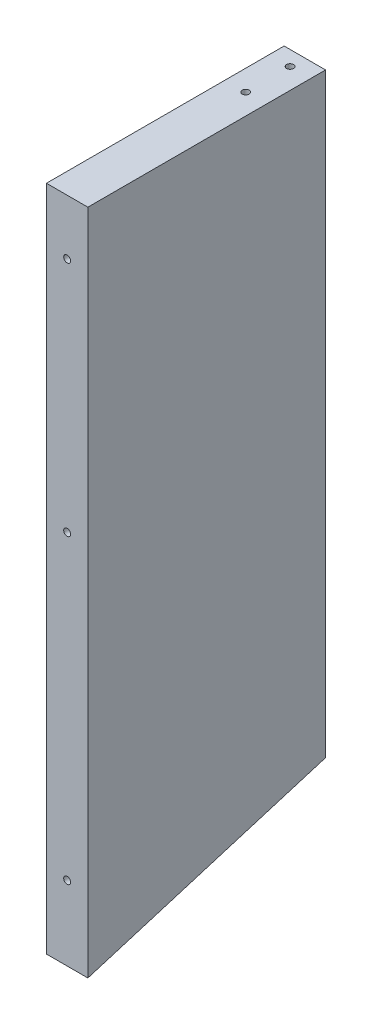
SolidWorks part; units mm, degrees
material "Beech"
ref_plane "Front Plane" through (0, 0, 0) normal (0, 0, 1) x (1, 0, 0)
ref_plane "Top Plane" through (0, 0, 0) normal (0, 1, 0) x (1, 0, 0)
ref_plane "Right Plane" through (0, 0, 0) normal (1, 0, 0) x (0, 0, -1)
sketch "Sketch1" plane through (0, 0, 0) normal (0, 0, 1) x (1, 0, 0)
  line L0 (-124.0045, -157.3) -> (-124.0045, -427.3421) construction
  line L1 (-124.0045, -157.3) -> (-124.0045, -144.6) construction
  line L2 (-244.0045, -144.6) -> (-4.0045, -144.6) construction
  line L7 (93.2955, -427.3421) -> (-341.3045, -427.3421) construction
  line L9 (8.6955, -157.3) -> (-256.7045, -157.3) construction
  line L10 (-133.5295, -157.3) -> (-133.5295, -427.3421)
  line L11 (-114.4795, -157.3) -> (-114.4795, -427.3421)
  line L12 (-133.5295, -157.3) -> (-114.4795, -157.3)
  line L13 (-133.5295, -427.3421) -> (-114.4795, -427.3421)
  dimension "D1" = 9.525
  dimension "D2" = 9.525
extrude "Boss-Extrude1" add sketch "Sketch1" along normal up to surface (33.95 mm away)
sketch "Sketch2" plane through (0, 0, 33.95) normal (0, 0, 1) x (1, 0, 0)
  line L0 (-256.7045, -157.3) -> (8.6955, -157.3) construction
  line L4 (-114.4795, -427.3421) -> (-114.4795, -157.3)
  line L5 (-114.4795, -157.3) -> (-133.5295, -157.3)
  line L6 (-133.5295, -157.3) -> (-133.5295, -427.3421)
  line L7 (-133.5295, -427.3421) -> (-114.4795, -427.3421)
  line L8 (-114.4795, -427.3421) -> (-114.4795, -157.3)
  line L9 (-114.4795, -157.3) -> (-133.5295, -157.3)
  line L10 (-133.5295, -157.3) -> (-133.5295, -427.3421)
  line L11 (-133.5295, -427.3421) -> (-114.4795, -427.3421)
  dimension "D1" = 0
extrude "Boss-Extrude2" add sketch "Sketch2" along normal up to surface (75.35 mm away)
sketch "Sketch3" plane through (-133.5295, 0, 0) normal (-1, 0, 0) x (0, 0, 1)
  line L0 (109.3, -427.3421) -> (109.3, -464.2661)
  line L1 (109.3, -464.2661) -> (0, -431.1858)
  line L2 (0, -431.1858) -> (0, -427.3421)
  line L3 (0, -427.3421) -> (109.3, -427.3421)
  line L4 (109.3, -427.3421) -> (0, -427.3421) construction
  line L5 (-12.7, -427.3421) -> (522.1409, -589.2145) construction
extrude "Boss-Extrude3" add sketch "Sketch3" against normal through all
hole_wizard "Hole1" positions "Sketch4" profile "Sketch5" legacy
sketch "Sketch4" plane through (-124.0045, 10.4243, 122) normal (0, 0, 1) x (-1, 0, 0)
  line L1 (0, 465.9538) -> (0, 167.7243) construction
  point P1 (113.65, 128.8076)
  point P3 (113.65, 23.941)
  point P5 (-94.6, 161.3743)
  point P7 (94.6, 161.3743)
  point P9 (0, 161.3743)
  point P11 (0, 193.1243)
  point P13 (0, 440.5538)
  point P15 (0, 301.9704)
  point P17 (40.9792, 301.9704)
  point P19 (166.7958, 301.9704)
  point P21 (207.775, 440.5538)
  point P23 (207.775, 333.0214)
  point P25 (207.775, 225.489)
  point P27 (207.775, 137.4243)
  point P29 (207.775, 10.4243)
  point P33 (-207.775, 10.4243)
  point P34 (-207.775, 137.4243)
  point P35 (-207.775, 225.489)
  point P36 (-207.775, 333.0214)
  point P37 (-207.775, 440.5538)
  point P38 (-166.7958, 301.9704)
  point P39 (-40.9792, 301.9704)
  point P40 (-113.65, 23.941)
  point P41 (-113.65, 128.8076)
sketch "Sketch5" plane through (-237.6545, -118.3833, 122) normal (1, 0, 0) x (0, -1, 0)
  line L0 (0, 0) -> (0, 32.7039)
  line L1 (0, 32.7039) -> (1.5875, 31.75)
  line L2 (1.5875, 31.75) -> (1.5875, 4.0177)
  line L3 (1.5875, 4.0177) -> (5.08, 0)
  line L4 (5.08, 0) -> (0, 0)
  line L5 (0, -14.3089) -> (0, 102.4216) construction
  line L6 (0, 32.7039) -> (-1.5875, 31.75) construction
  line L7 (-1.5875, 4.0177) -> (-5.08, 0) construction
  dimension "Diameter" = 3.175
  dimension "Depth" = 31.75
  dimension "C-Sink Diameter" = 10.16
  dimension "C-Sink Angle" = 82
  dimension "Drill Angle" = 118
hole_wizard "Hole3" positions "Sketch7" profile "Sketch8" legacy
sketch "Sketch7" plane through (-124.0045, -144.6, -155.2867) normal (0, 1, 0) x (-1, 0, 0)
  line L0 (0, 155.2867) -> (0, 189.2867) construction
  line L9 (0, 189.2867) -> (0, 182.4867)
  line L10 (0, 182.4867) -> (0, 175.6867)
  line L11 (0, 175.6867) -> (0, 168.8867)
  line L12 (0, 168.8867) -> (0, 162.0867)
  line L13 (0, 162.0867) -> (0, 155.2867)
  point P26 (0, 182.4867)
  point P32 (0, 162.0867)
sketch "Sketch8" plane through (-124.0045, -144.6, 6.8) normal (1, 0, 0) x (0, 0, 1)
  line L0 (0, 0) -> (0, 32.7039)
  line L1 (0, 32.7039) -> (1.5875, 31.75)
  line L2 (1.5875, 31.75) -> (1.5875, 4.0177)
  line L3 (1.5875, 4.0177) -> (5.08, 0)
  line L4 (5.08, 0) -> (0, 0)
  line L5 (0, -14.3089) -> (0, 102.4216) construction
  line L6 (0, 32.7039) -> (-1.5875, 31.75) construction
  line L7 (-1.5875, 4.0177) -> (-5.08, 0) construction
  dimension "Diameter" = 3.175
  dimension "Depth" = 31.75
  dimension "C-Sink Diameter" = 10.16
  dimension "C-Sink Angle" = 82
  dimension "Drill Angle" = 118
hole_wizard "Hole4" positions "Sketch9" profile "Sketch10" legacy
sketch "Sketch9" plane through (-124.0045, 10.4243, -12.7) normal (0, 0, -1) x (1, 0, 0)
  line L12 (0, 0) -> (0, 155.0243) construction
  point P0 (-207.775, 333.0214)
  point P3 (-207.775, 225.489)
  point P6 (-207.775, 137.4243)
  point P9 (-172.1667, 4.0743)
  point P12 (-146.0833, 4.0743)
  point P15 (-94.6, 161.3743)
  point P18 (0, 161.3743)
  point P21 (94.6, 161.3743)
  point P24 (146.0833, 4.0743)
  point P27 (172.1667, 4.0743)
  point P30 (207.775, 137.4243)
  point P33 (207.775, 225.489)
  point P36 (207.775, 333.0214)
  point P39 (166.7958, 301.9704)
  point P42 (40.9792, 301.9704)
  point P45 (-40.9792, 301.9704)
  point P48 (-166.7958, 301.9704)
  point P51 (0, 193.1243)
  point P54 (0, 301.9704)
  point P57 (0, 412.3664)
  point P80 (-126.35, 106.8243)
  point P82 (-126.35, 58.6243)
  point P96 (126.35, 58.6243)
  point P97 (126.35, 106.8243)
sketch "Sketch10" plane through (-331.7795, -322.5971, -12.7) normal (1, 0, 0) x (0, 1, 0)
  line L0 (0, 0) -> (0, 32.7039)
  line L1 (0, 32.7039) -> (1.5875, 31.75)
  line L2 (1.5875, 31.75) -> (1.5875, 4.0177)
  line L3 (1.5875, 4.0177) -> (5.08, 0)
  line L4 (5.08, 0) -> (0, 0)
  line L5 (0, -14.3089) -> (0, 102.4216) construction
  line L6 (0, 32.7039) -> (-1.5875, 31.75) construction
  line L7 (-1.5875, 4.0177) -> (-5.08, 0) construction
  dimension "Diameter" = 3.175
  dimension "Depth" = 31.75
  dimension "C-Sink Diameter" = 10.16
  dimension "C-Sink Angle" = 82
  dimension "Drill Angle" = 118
hole_wizard "Hole5" positions "Sketch11" profile "Sketch12" legacy
sketch "Sketch11" plane through (-124.0045, -363.2296, -268.3751) normal (0, -0.9571, -0.2897) x (1, 0, 0)
  line L4 (-207.775, 822.0847) -> (-207.775, 404.0189) construction
  line L8 (-207.775, 822.0847) -> (-207.775, 717.5683)
  line L9 (-207.775, 717.5683) -> (-207.775, 613.0518)
  line L10 (-207.775, 613.0518) -> (-207.775, 508.5353)
  line L11 (-207.775, 508.5353) -> (-207.775, 404.0189)
  line L12 (-108.65, 822.0847) -> (-108.65, 404.0189) construction
  line L15 (0, 822.0847) -> (0, 692.6022) construction
  line L18 (-207.775, 390.7499) -> (-207.775, 276.5537) construction
  line L22 (-207.775, 390.7499) -> (-207.775, 362.2009)
  line L23 (-207.775, 362.2009) -> (-207.775, 333.6518)
  line L24 (-207.775, 333.6518) -> (-207.775, 305.1027)
  line L25 (-207.775, 305.1027) -> (-207.775, 276.5537)
  line L26 (0, 390.7499) -> (0, 276.5537) construction
  line L30 (0, 276.5537) -> (0, 305.1027)
  line L31 (0, 305.1027) -> (0, 333.6518)
  line L32 (0, 333.6518) -> (0, 362.2009)
  line L33 (0, 362.2009) -> (0, 390.7499)
  point P24 (-207.775, 613.0518)
  point P31 (-207.775, 456.2771)
  point P33 (-207.775, 769.8265)
  point P52 (-108.65, 456.2771)
  point P54 (-108.65, 613.0518)
  point P56 (-108.65, 769.8265)
  point P76 (-207.775, 362.2009)
  point P80 (-207.775, 305.1027)
  point P99 (0, 305.1027)
  point P104 (0, 362.2009)
  point P113 (207.775, 305.1027)
  point P114 (207.775, 362.2009)
  point P115 (108.65, 769.8265)
  point P116 (108.65, 613.0518)
  point P117 (108.65, 456.2771)
  point P118 (207.775, 769.8265)
  point P119 (207.775, 456.2771)
  point P120 (207.775, 613.0518)
sketch "Sketch12" plane through (83.7705, -540.8176, 318.3915) normal (1, 0, 0) x (0, 0.2897, -0.9571)
  line L0 (0, 0) -> (0, 32.7039)
  line L1 (0, 32.7039) -> (1.5875, 31.75)
  line L2 (1.5875, 31.75) -> (1.5875, 4.0177)
  line L3 (1.5875, 4.0177) -> (5.08, 0)
  line L4 (5.08, 0) -> (0, 0)
  line L5 (0, -14.3089) -> (0, 102.4216) construction
  line L6 (0, 32.7039) -> (-1.5875, 31.75) construction
  line L7 (-1.5875, 4.0177) -> (-5.08, 0) construction
  dimension "Diameter" = 3.175
  dimension "Depth" = 31.75
  dimension "C-Sink Diameter" = 10.16
  dimension "C-Sink Angle" = 82
  dimension "Drill Angle" = 118
